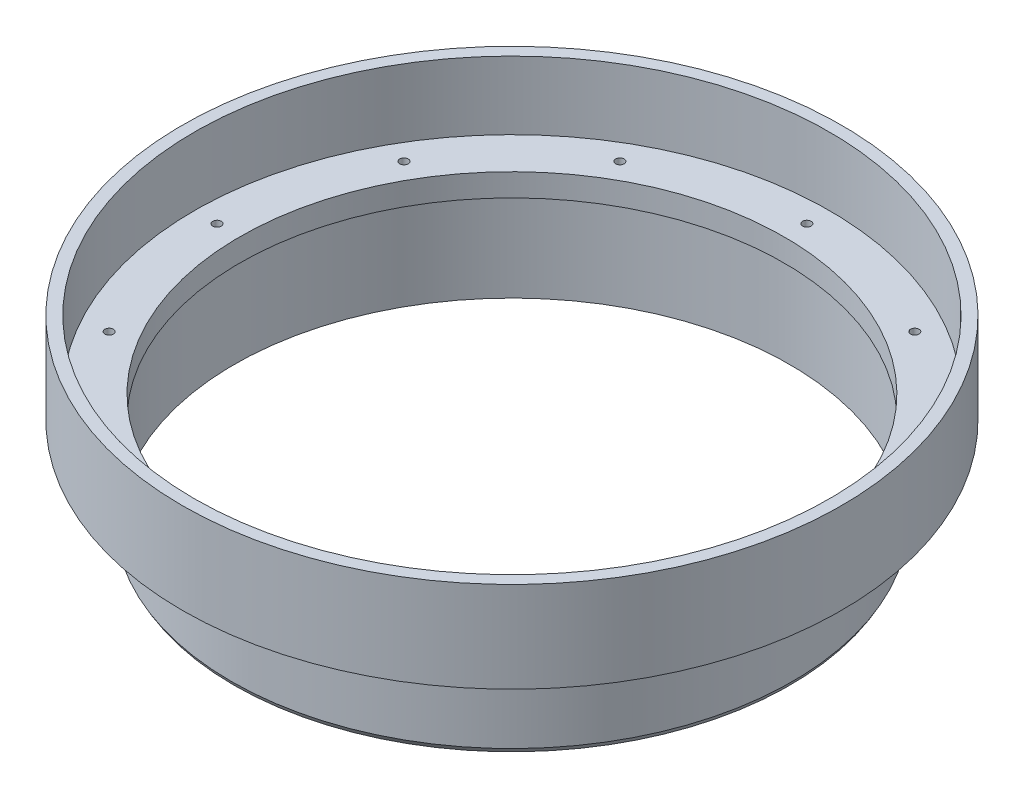
SolidWorks part; units mm, degrees
material "6061-T6 (SS)"
ref_plane "Front Plane" through (0, 0, 0) normal (0, 0, 1) x (1, 0, 0)
ref_plane "Top Plane" through (0, 0, 0) normal (0, 1, 0) x (1, 0, 0)
ref_plane "Right Plane" through (0, 0, 0) normal (1, 0, 0) x (0, 0, -1)
ref_axis "Axis1" through (0, 55, 0) along (0, -1, 0)
sketch "Cross Section" plane through (0, 0, 0) normal (0, 0, 1) x (1, 0, 0)
  line L0 (-38.1, 0) -> (-38.1, -3.175)
  line L1 (-38.1, -3.175) -> (-38.8874, -3.175)
  line L2 (-38.8874, -3.175) -> (-38.8874, -15.875)
  line L3 (-38.8874, -15.875) -> (-39.2684, -15.2151)
  line L4 (0, -15.875) -> (-38.1, -15.875) construction
  line L5 (-39.2684, -15.2151) -> (-39.2684, -3.175)
  line L6 (-39.2684, -3.175) -> (-46.1264, -3.175)
  line L7 (-46.1264, -3.175) -> (-46.1264, 9.525)
  line L8 (-46.1264, 9.525) -> (-44.45, 9.525)
  line L9 (-44.45, 9.525) -> (-44.45, 0)
  line L10 (-44.45, 0) -> (-38.1, 0)
  line L11 (-38.1, 0) -> (0, 0) construction
  line L12 (0, 55) -> (0, -55) construction
  line L14 (-44.45, 1.5875) -> (-44.45, 3.175) construction
  dimension "D1" = 0.7874
  dimension "D3" = 0.381
  dimension "D4" = 30
  dimension "D5" = 6.858
  dimension "D6" = 12.7
  dimension "D9" = 3.175
  dimension "D8" = 38.1
revolve "Main" add sketch "Cross Section" angle 360 about axis through (0, 55, 0) along (0, -1, 0)
sketch "Hole Location" plane through (0, 0, 0) normal (0, 1, 0) x (1, 0, 0)
  line L0 (0, 0) -> (-41.275, 0) construction
  circle A0 centre (0, 0) radius 41.275 construction
  dimension "D1" = 82.55
hole_wizard "#0-80 Tapped Hole1" positions "Sketch5" profile "Sketch7" tap size "#0-80" standard "ANSI Inch"
sketch "Sketch5" plane through (0, 0, 0) normal (0, 1, 0) x (1, 0, 0)
  point P0 (-41.275, 0)
sketch "Sketch7" plane through (-41.275, 0, 0) normal (1, 0, 0) x (0, 0, 1)
  line L0 (0, 0) -> (0, 3.5329)
  line L1 (0, 3.5329) -> (0.5956, 3.175)
  line L2 (0.5956, 3.175) -> (0.5956, 0)
  line L5 (0.5956, 0) -> (0, 0)
  line L10 (0, 3.5329) -> (-0.5956, 3.175) construction
  line L11 (0, -6.35) -> (0, 107.95) construction
  dimension "Tap Drill Dia." = 1.1913
  dimension "Tap Drill Depth" = 3.175
  dimension "Drill Angle" = 118
cosmetic thread "Hole Thread1" parameters "D1"=3.048, "D2"=1.524
pattern_circular "Screw Holes" count 12 over 360 about axis through (0, 55, 0) along (0, -1, 0) of "#0-80 Tapped Hole1"
equation "\"D8@Cross Section\"=\"TANK DIAMETER@Cryo Tank.Assembly\"/2"
equation "\"D1@Hole Location\"=\"TANK DIAMETER@Cryo Tank.Assembly\"+\"GASKET SEAT THICKNESS@Cryo Tank.Assembly\""
equation "\"D1@Cross Section\"=\"LINER THICKNESS@Cryo Tank.Assembly\""
equation "\"D3@Cross Section\"=\"ALUMINUM LAP THICKNESS@Cryo Tank.Assembly\""
equation "\"D5@Cross Section\"=2*\"CF THICKNESS@Cryo Tank.Assembly\"+\"NOMEX THICKNESS@Cryo Tank.Assembly\""
